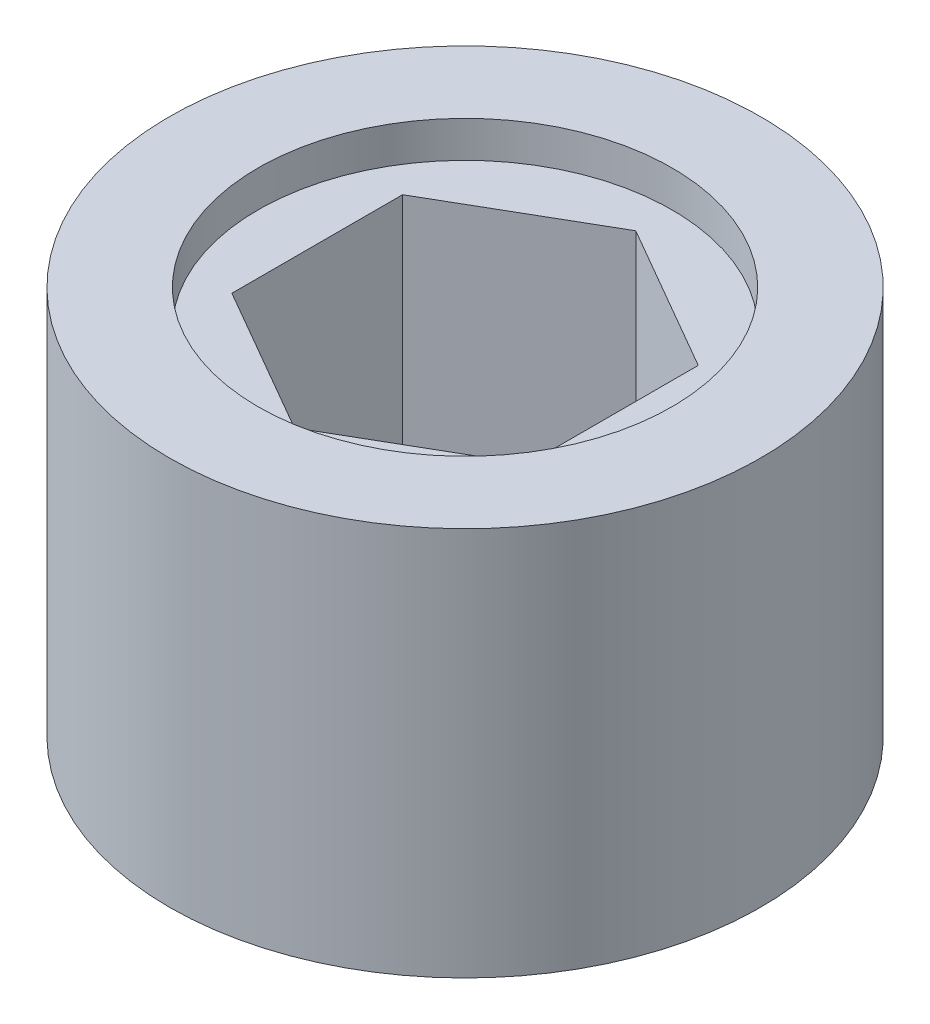
SolidWorks part; units mm, degrees
material "ABS PC"
ref_plane "Front Plane" through (0, 0, 0) normal (0, 0, 1) x (1, 0, 0)
ref_plane "Top Plane" through (0, 0, 0) normal (0, 1, 0) x (1, 0, 0)
ref_plane "Right Plane" through (0, 0, 0) normal (1, 0, 0) x (0, 0, -1)
sketch "Sketch1" plane through (0, 0, 0) normal (0, 1, 0) x (1, 0, 0)
  line L1 (6.35, 3.6662) -> (0, 7.3323)
  line L2 (0, 7.3323) -> (-6.35, 3.6662)
  line L3 (-6.35, 3.6662) -> (-6.35, -3.6662)
  line L4 (-6.35, -3.6662) -> (0, -7.3323)
  line L5 (0, -7.3323) -> (6.35, -3.6662)
  line L6 (6.35, -3.6662) -> (6.35, 3.6662)
  circle A0 centre (0, 0) radius 6.35 construction
  circle A1 centre (0, 0) radius 8.89
  circle A2 centre (0, 0) radius 12.7
  dimension "D1" = 12.7
  dimension "D2" = 17.78
  dimension "D3" = 25.4
extrude "Boss-Extrude1" add sketch "Sketch1" along normal blind 16.7132 contours A2 A1 region at (-12.3408, 0, 0)
extrude "Boss-Extrude2" add sketch "Sketch1<3>" along normal blind 15.1511 contours A1 L6 L5 L4 L3 L2 L1 region at (-8.6386, 0, 0)
sketch "Sketch1<3>" plane through (0, 0, 0) normal (0, 1, 0) x (1, 0, 0) same geometry as "Sketch1"
